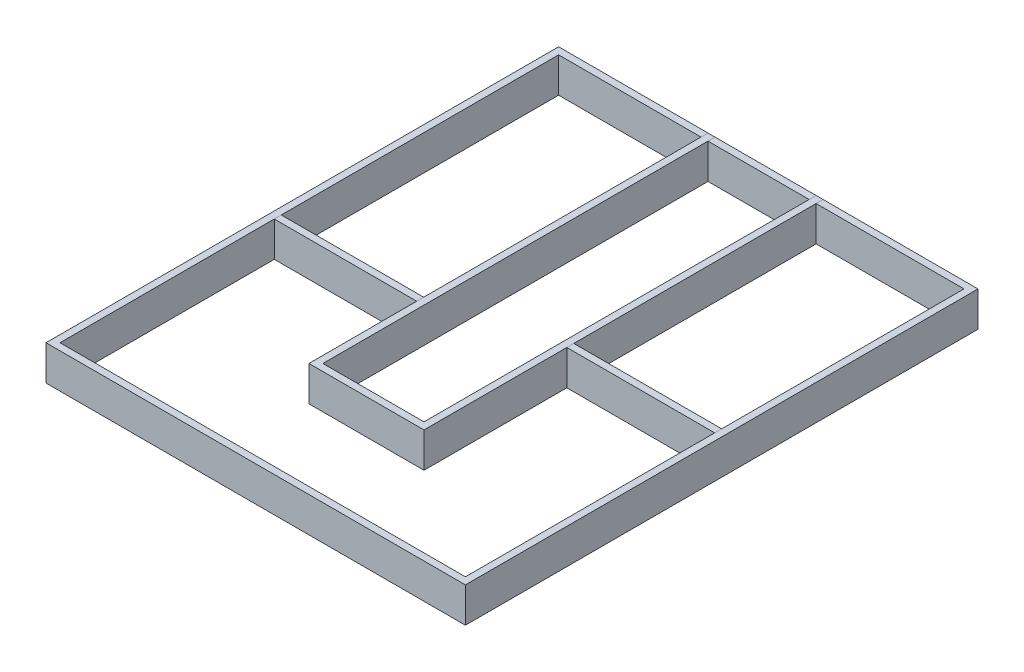
SolidWorks part; units mm, degrees
ref_plane "Спереди" through (0, 0, 0) normal (0, 0, 1) x (1, 0, 0)
ref_plane "Сверху" through (0, 0, 0) normal (0, 1, 0) x (1, 0, 0)
ref_plane "Справа" through (0, 0, 0) normal (1, 0, 0) x (0, 0, -1)
sketch "Эскиз1" plane through (0, 0, 0) normal (0, 1, 0) x (1, 0, 0)
  line L0 (-25.8758, 110) -> (-25.8758, -61.2917)
  line L1 (-90, 110) -> (90, 110)
  line L2 (-90, 110) -> (-90, -110)
  line L3 (-90, -110) -> (90, -110)
  line L4 (90, 110) -> (90, -110)
  line L5 (-90, 110) -> (90, -110) construction
  line L6 (-90, -110) -> (90, 110) construction
  line L7 (-25.8758, -61.2917) -> (23.5235, -61.2917)
  line L8 (23.5235, -61.2917) -> (23.5235, 110)
  line L9 (-90, -15.0289) -> (-25.8758, -15.0289)
  line L10 (23.5235, 0) -> (90, 0)
  point P0 (0, 0)
extrude "Вытянуть-Тонкостенный1" add sketch "Эскиз1" along normal blind 15 thin thin type one direction reverse wall 3
